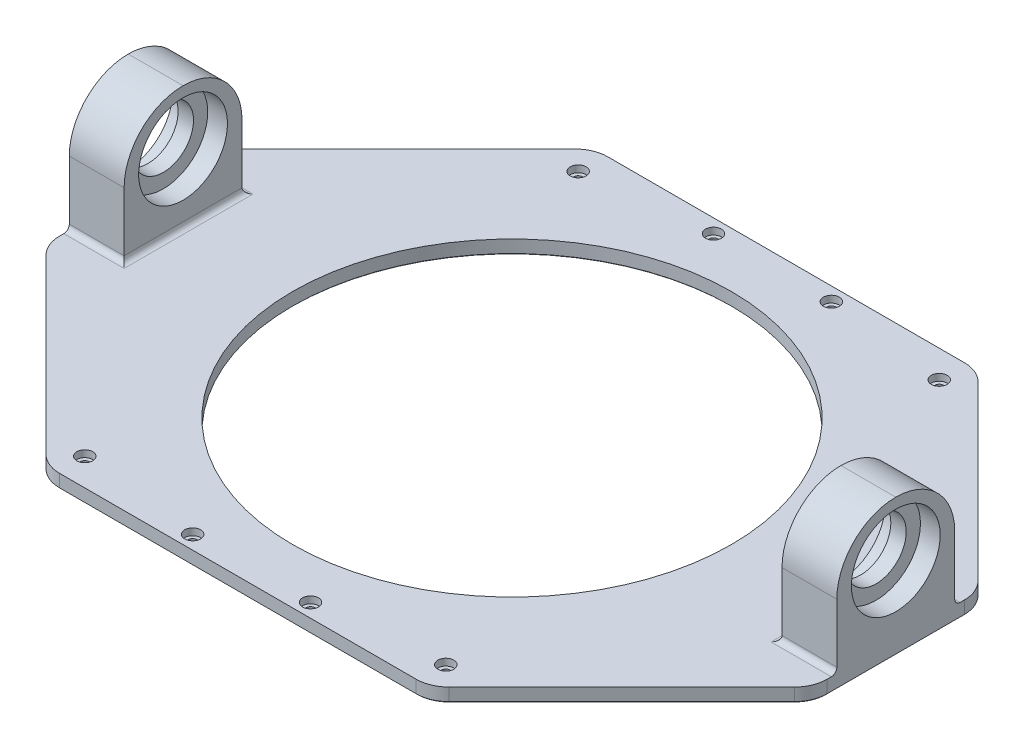
SolidWorks part; units mm, degrees
ref_plane "前视基准面" through (0, 0, 0) normal (0, 0, 1) x (1, 0, 0)
ref_plane "上视基准面" through (0, 0, 0) normal (0, 1, 0) x (1, 0, 0)
ref_plane "右视基准面" through (0, 0, 0) normal (1, 0, 0) x (0, 0, -1)
other "Configuration Table"
sketch "草图1" plane through (0, 0, 0) normal (0, 1, 0) x (1, 0, 0)
  line L1 (0, 0) -> (280, 0)
  line L2 (0, 0) -> (0, -280)
  line L3 (0, -280) -> (280, -280)
  line L4 (280, 0) -> (280, -280)
  dimension "D1" = 280
  dimension "D2" = 280
extrude "凸台-拉伸1" add sketch "草图1" along normal blind 5
sketch "草图2" plane through (0, 5, 0) normal (0, 1, 0) x (1, 0, 0)
  line L0 (0, -280) -> (280, -280) construction
  circle A0 centre (140, -180) radius 80
  point P4 (140, -280)
  dimension "D1" = 160
  dimension "D2" = 0
  dimension "D3" = 100
extrude "切除-拉伸1" cut sketch "草图2" against normal blind 5
sketch "草图3" plane through (0, 5, 0) normal (0, 1, 0) x (1, 0, 0)
  line L0 (0, 0) -> (0, -280) construction
  line L1 (0, -158.5) -> (20, -158.5)
  line L2 (0, -158.5) -> (0, -201.5)
  line L3 (0, -201.5) -> (20, -201.5)
  line L4 (20, -158.5) -> (20, -201.5)
  line L5 (280, -280) -> (280, 0) construction
  line L6 (280, -158.5) -> (260, -158.5)
  line L7 (280, -158.5) -> (280, -201.5)
  line L8 (280, -201.5) -> (260, -201.5)
  line L9 (260, -158.5) -> (260, -201.5)
  circle A0 centre (140, -180) radius 80 construction
  point P12 (20, -180)
  point P15 (260, -180)
  dimension "D1" = 0
  dimension "D2" = 0
  dimension "D3" = 43
  dimension "D4" = 43
  dimension "D5" = 20
  dimension "D6" = 20
extrude "凸台-拉伸2" add sketch "草图3" along normal blind 45
sketch "草图4" plane through (280, 0, 0) normal (1, 0, 0) x (0, 0, -1)
  line L0 (-201.5, 50) -> (-158.5, 50) construction
  circle A0 centre (-180, 30) radius 11
  point P4 (-180, 50)
  dimension "D1" = 0
  dimension "12.5" = 22
  dimension "D2" = 20
extrude "切除-拉伸2" cut sketch "草图4" against normal through all
sketch "草图5" plane through (280, 0, 0) normal (1, 0, 0) x (0, 0, -1)
  circle A0 centre (-180, 30) radius 16.2
  dimension "D1" = 32.4
extrude "切除-拉伸3" cut sketch "草图5" against normal blind 7.2
sketch "草图6" plane through (260, 0, 0) normal (-1, 0, 0) x (0, 0, 1)
  circle A0 centre (180, 30) radius 16.2
  dimension "D1" = 32.4
extrude "切除-拉伸4" cut sketch "草图6" against normal blind 7.2
sketch "草图7" plane through (20, 0, 0) normal (1, 0, 0) x (0, 0, -1)
  circle A0 centre (-180, 30) radius 16.2
  dimension "D1" = 32.4
extrude "切除-拉伸5" cut sketch "草图7" against normal blind 7.2
sketch "草图8" plane through (0, 0, 0) normal (-1, 0, 0) x (0, 0, 1)
  circle A0 centre (180, 30) radius 16.2
  dimension "D1" = 32.4
extrude "切除-拉伸6" cut sketch "草图8" against normal blind 7.2
sketch "草图9" plane through (0, 5, 0) normal (0, 1, 0) x (1, 0, 0)
  line L0 (280, -158.5) -> (280, 0) construction
  line L1 (0, 0) -> (280, 0)
  line L2 (0, 0) -> (0, -80)
  line L3 (0, -80) -> (280, -80)
  line L4 (280, 0) -> (280, -80)
  circle A0 centre (140, -180) radius 80 construction
  dimension "D1" = 100
extrude "切除-拉伸7" cut sketch "草图9" against normal through all
chamfer "倒角1" distance 70 angle 45 4 edges at (280, 2.5, 80) (280, 2.5, 280) (0, 2.5, 280) (0, 2.5, 80)
fillet "圆角1" radius 21.5 4 edges at (270, 50, 201.5) (270, 50, 158.5) (10, 50, 201.5) (10, 50, 158.5)
fillet "圆角2" radius 12 8 edges at (70, 2.5, 80) (210, 2.5, 80) (280, 2.5, 150) (280, 2.5, 210) (210, 2.5, 280) (70, 2.5, 280) (0, 2.5, 210) (0, 2.5, 150)
fillet "圆角3" radius 2 6 edges at (260, 5, 180) (270, 5, 201.5) (270, 5, 158.5) (10, 5, 158.5) (20, 5, 180) (10, 5, 201.5)
sketch "草图10" plane through (0, 0, 0) normal (0, -1, 0) x (-1, 0, 0)
  line L1 (-140, -80) -> (-140, -118.5005) construction
  line L3 (0, -154.9706) -> (0, -205.0294) construction
  line L4 (-74.9706, -80) -> (-205.0294, -80) construction
  circle A0 centre (-20, -187.5) radius 1.6
  circle A1 centre (-20, -172.5) radius 1.6
  circle A5 centre (-260, -187.5) radius 1.6
  circle A6 centre (-260, -172.5) radius 1.6
  circle A7 centre (-140, -180) radius 80 construction
  dimension "D1" = 3.2
  dimension "D2" = 3.2
  dimension "D4" = 20
  dimension "D5" = 15
  dimension "D6" = 7.5
  dimension "D3" = 20
extrude "切除-拉伸8" cut sketch "草图10" against normal blind 5
sketch "草图11" plane through (0, 0, 0) normal (0, -1, 0) x (-1, 0, 0)
  circle A4 centre (-20, -172.5) radius 2.35
  circle A5 centre (-20, -187.5) radius 2.35
  circle A6 centre (-260, -172.5) radius 2.35
  circle A7 centre (-260, -187.5) radius 2.35
  dimension "D1" = 4.7
  dimension "D2" = 4.7
  dimension "D3" = 4.7
  dimension "D4" = 4.7
extrude "切除-拉伸9" cut sketch "草图11" against normal blind 4.2
sketch "草图12" plane through (0, 5, 0) normal (0, 1, 0) x (1, 0, 0)
  line L0 (35.645, -180) -> (233.9972, -180) construction
  circle A0 centre (118.5, -85) radius 1.65
  circle A1 centre (161.5, -85) radius 1.65
  circle A2 centre (161.5, -275) radius 1.65
  circle A3 centre (140, -180) radius 80 construction
  circle A4 centre (118.5, -275) radius 1.65
  dimension "D1" = 43
  dimension "D2" = 21.5
  dimension "D3" = 95
  dimension "D4" = 95
  dimension "D5" = 3.3
  dimension "D6" = 3.3
extrude "切除-拉伸10" cut sketch "草图12" against normal blind 10
sketch "草图13" plane through (0, 5, 0) normal (0, 1, 0) x (1, 0, 0)
  line L0 (41.8597, -180) -> (226.2288, -180) construction
  circle A0 centre (118.5, -85) radius 2.9
  circle A1 centre (161.5, -85) radius 2.9
  circle A2 centre (161.5, -275) radius 2.9
  circle A3 centre (118.5, -275) radius 2.9
  dimension "D1" = 5.8
  dimension "D2" = 5.8
extrude "切除-拉伸11" cut sketch "草图13" against normal blind 2.5
sketch "草图14" plane through (0, 5, 0) normal (0, 1, 0) x (1, 0, 0)
  line L0 (74.9706, -80) -> (205.0294, -80) construction
  line L1 (66.4853, -83.5147) -> (3.5147, -146.4853) construction
  line L2 (276.4853, -146.4853) -> (213.5147, -83.5147) construction
  line L3 (3.5147, -213.5147) -> (66.4853, -276.4853) construction
  line L4 (74.9706, -280) -> (205.0294, -280) construction
  line L5 (213.5147, -276.4853) -> (276.4853, -213.5147) construction
  circle A0 centre (74.1421, -90) radius 1.6
  circle A1 centre (74.1421, -270) radius 1.6
  circle A2 centre (205.8579, -270) radius 1.6
  circle A3 centre (205.8579, -90) radius 1.6
  dimension "D1" = 3.2
  dimension "D2" = 10
  dimension "D3" = 10
  dimension "D4" = 3.2
  dimension "D5" = 3.2
  dimension "D6" = 3.2
  dimension "D7" = 10
  dimension "D9" = 10
  dimension "D10" = 10
  dimension "D11" = 10
  dimension "D12" = 10
  dimension "D8" = 10
extrude "切除-拉伸12" cut sketch "草图14" against normal blind 10
sketch "草图15" plane through (0, 5, 0) normal (0, 1, 0) x (1, 0, 0)
  circle A0 centre (74.1421, -270) radius 2.9
  circle A1 centre (205.8579, -270) radius 2.9
  circle A2 centre (205.8579, -90) radius 2.9
  circle A3 centre (74.1421, -90) radius 2.9
  dimension "D1" = 5.8
  dimension "D2" = 5.8
  dimension "D3" = 5.8
  dimension "D4" = 5.8
extrude "切除-拉伸13" cut sketch "草图15" against normal blind 2.5
chamfer "倒角4" distance 0.4 angle 45 29 edges at (0.9134, 0, 150.3784) (0, 0, 180) (0.9134, 0, 209.6216) (35, 0, 245) (70.3784, 0, 279.0866) (140, 0, 280) (209.6216, 0, 279.0866) (245, 0, 245) (279.0866, 0, 209.6216) (280, 0, 180) (279.0866, 0, 150.3784) (245, 0, 115) (209.6216, 0, 80.9134) (140, 0, 80) (70.3784, 0, 80.9134) (35, 0, 115) (140, 0, 260) (20, 0, 170.15) (260, 0, 185.15) (260, 0, 170.15) (20, 0, 185.15) (161.5, 0, 86.65) (118.5, 0, 86.65) (74.1421, 0, 91.6) (74.1421, 0, 271.6) (205.8579, 0, 271.6) (205.8579, 0, 91.6) (161.5, 0, 276.65) (118.5, 0, 276.65)
